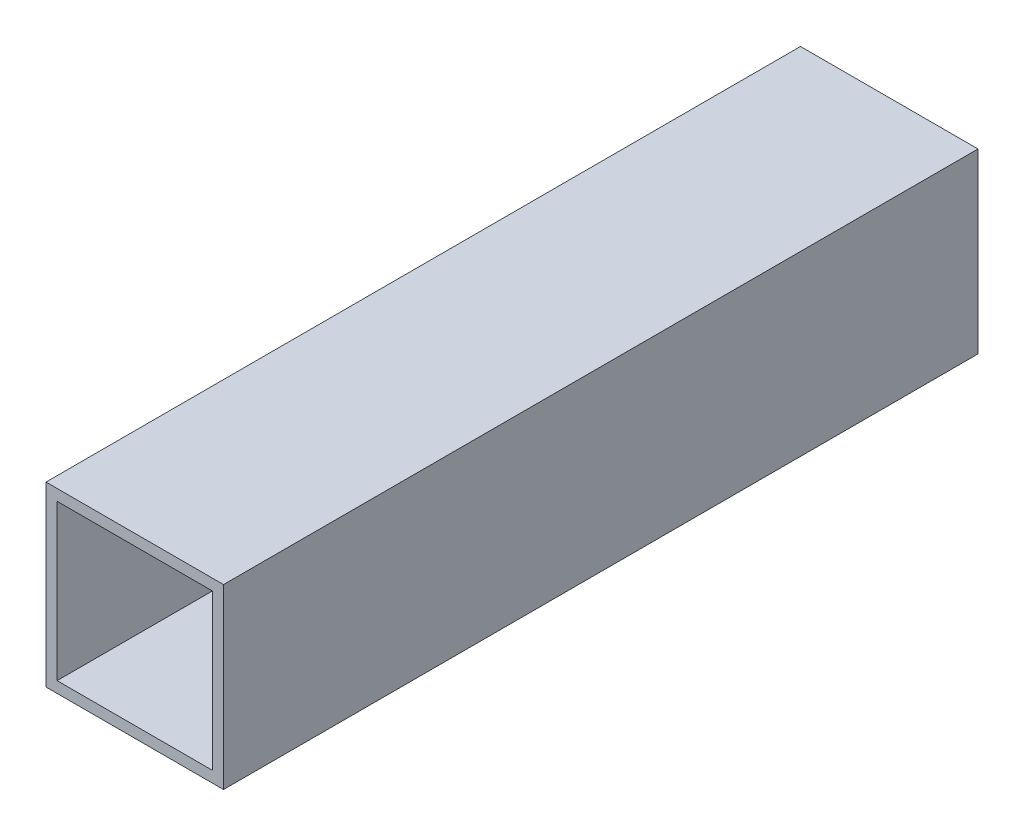
SolidWorks part; units mm, degrees
ref_plane "Front Plane" through (0, 0, 0) normal (0, 0, 1) x (1, 0, 0)
ref_plane "Top Plane" through (0, 0, 0) normal (0, 1, 0) x (1, 0, 0)
ref_plane "Right Plane" through (0, 0, 0) normal (1, 0, 0) x (0, 0, -1)
sketch "Sketch1" plane through (0, 0, 0) normal (0, 0, 1) x (1, 0, 0)
  line L0 (-22.225, 22.225) -> (22.225, 22.225)
  line L1 (-25.4, -25.4) -> (25.4, -25.4)
  line L2 (-25.4, -25.4) -> (-25.4, 25.4)
  line L3 (-25.4, 25.4) -> (25.4, 25.4)
  line L4 (25.4, -25.4) -> (25.4, 25.4)
  line L5 (-25.4, -25.4) -> (25.4, 25.4) construction
  line L6 (-25.4, 25.4) -> (25.4, -25.4) construction
  line L7 (22.225, -22.225) -> (22.225, 22.225)
  line L8 (-22.225, -22.225) -> (22.225, -22.225)
  line L9 (-22.225, -22.225) -> (-22.225, 22.225)
  point P0 (0, 0)
  dimension "D1" = 3.175
  dimension "tube_width" = 50.8
  dimension "D2" = 50.8
extrude "Boss-Extrude1" add sketch "Sketch1" along normal blind 215.9
ref_axis "Axis1" through (0, 0, -10.795) along (0, 0, 1)
